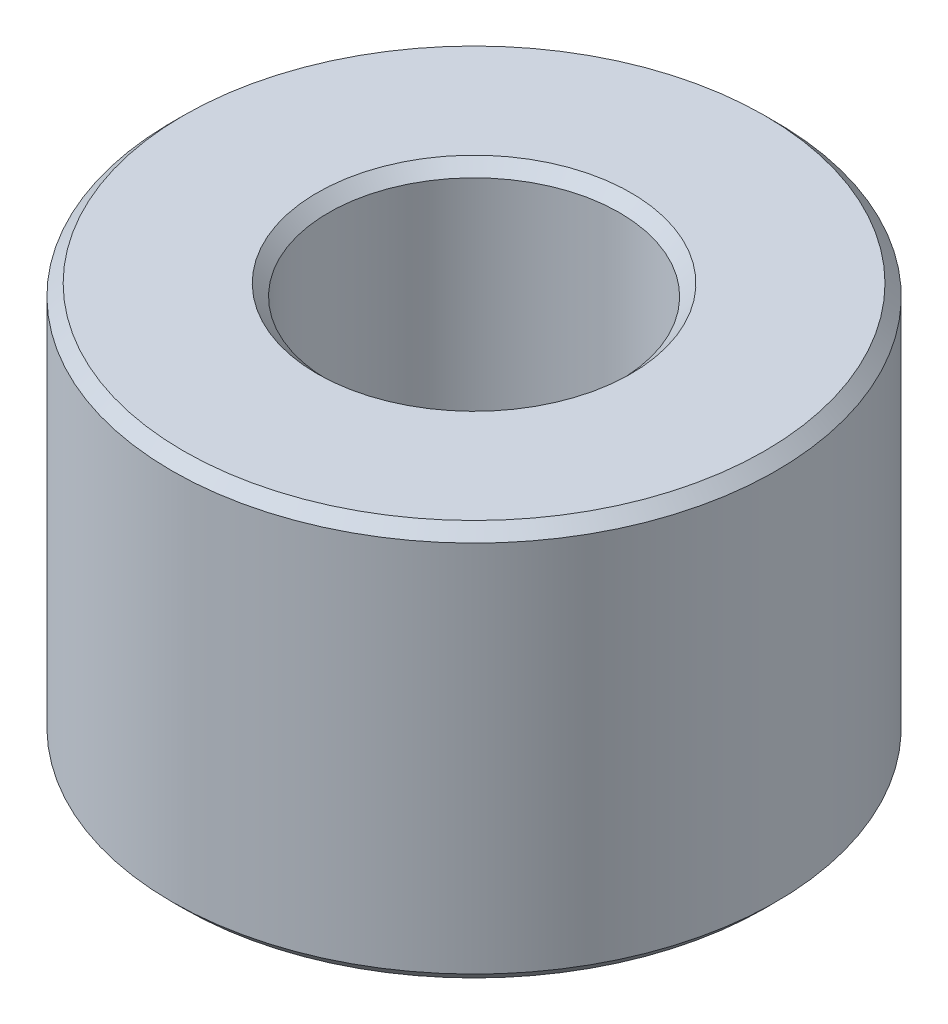
SolidWorks part; units mm, degrees
ref_plane "Front Plane" through (0, 0, 0) normal (0, 0, 1) x (1, 0, 0)
ref_plane "Top Plane" through (0, 0, 0) normal (0, 1, 0) x (1, 0, 0)
ref_plane "Right Plane" through (0, 0, 0) normal (1, 0, 0) x (0, 0, -1)
sketch "Sketch1" plane through (0, 0, 0) normal (0, 1, 0) x (1, 0, 0)
  circle A0 centre (0, 0) radius 27.5
  dimension "SLEEVE_OD" = 55
extrude "Boss-Extrude1" add sketch "Sketch1" along normal blind 36.0705
sketch "Sketch2" plane through (0, 0, 0) normal (0, 1, 0) x (1, 0, 0)
  circle A0 centre (0, 0) radius 13.2361
  dimension "BORE_D" = 26.4722
extrude "Cut-Extrude1" cut sketch "Sketch2" along normal through all
chamfer "Chamfer1" distance 1.0452 angle 45 4 edges at (0, 36.0705, 13.2361) (0, 0, 13.2361) (0, 0, 27.5) (0, 36.0705, 27.5)
